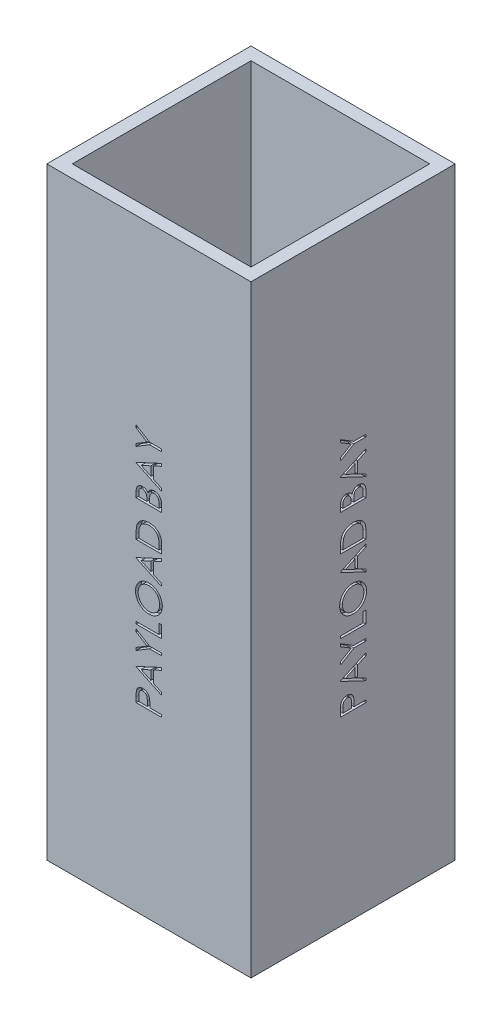
SolidWorks part; units mm, degrees
material "PVC Rigid"
ref_plane "Front Plane" through (0, 0, 0) normal (0, 0, 1) x (1, 0, 0)
ref_plane "Top Plane" through (0, 0, 0) normal (0, 1, 0) x (1, 0, 0)
ref_plane "Right Plane" through (0, 0, 0) normal (1, 0, 0) x (0, 0, -1)
sketch "Sketch1" plane through (0, 0, 0) normal (0, 1, 0) x (1, 0, 0)
  line L1 (-50.8, -50.8) -> (50.8, -50.8)
  line L2 (-50.8, -50.8) -> (-50.8, 50.8)
  line L3 (-50.8, 50.8) -> (50.8, 50.8)
  line L4 (50.8, -50.8) -> (50.8, 50.8)
  line L5 (-50.8, -50.8) -> (50.8, 50.8) construction
  line L6 (-50.8, 50.8) -> (50.8, -50.8) construction
  line L7 (-44.45, -44.45) -> (44.45, -44.45)
  line L8 (-44.45, -44.45) -> (-44.45, 44.45)
  line L9 (-44.45, 44.45) -> (44.45, 44.45)
  line L10 (44.45, -44.45) -> (44.45, 44.45)
  line L11 (-44.45, -44.45) -> (44.45, 44.45) construction
  line L12 (-44.45, 44.45) -> (44.45, -44.45) construction
  point P0 (0, 0)
  point P6 (0, 0)
  dimension "D1" = 101.6
  dimension "D2" = 101.6
  dimension "D3" = 88.9
extrude "Boss-Extrude1" add sketch "Sketch1" along normal blind 300
sketch "Sketch6" plane through (-50.8, 0, 0) normal (-1, 0, 0) x (0, 0, 1)
  line L0 (6.35, 0) -> (6.35, 300) construction
  line L1 (-50.8, 0) -> (50.8, 0) construction
  line L2 (-50.8, 300) -> (50.8, 300) construction
  line L3 (-50.8, 300) -> (-50.8, 0) construction
  text T0 "PAYLOAD BAY" font "Century Gothic" height in points 48
  dimension "D1" = 57.15
extrude "Cut-Extrude1" cut sketch "Sketch6" against normal blind 2.54
sketch "Sketch7" plane through (0, 0, 0) normal (0, 0, 1) x (1, 0, 0)
  line L0 (0, 0) -> (0, 300) construction
  line L1 (-50.8, 300) -> (50.8, 300) construction
pattern_circular "CirPattern1" count 4 over 360 about axis through (0, 0, 0) along (0, 1, 0) of "Cut-Extrude1" reverse direction yes
